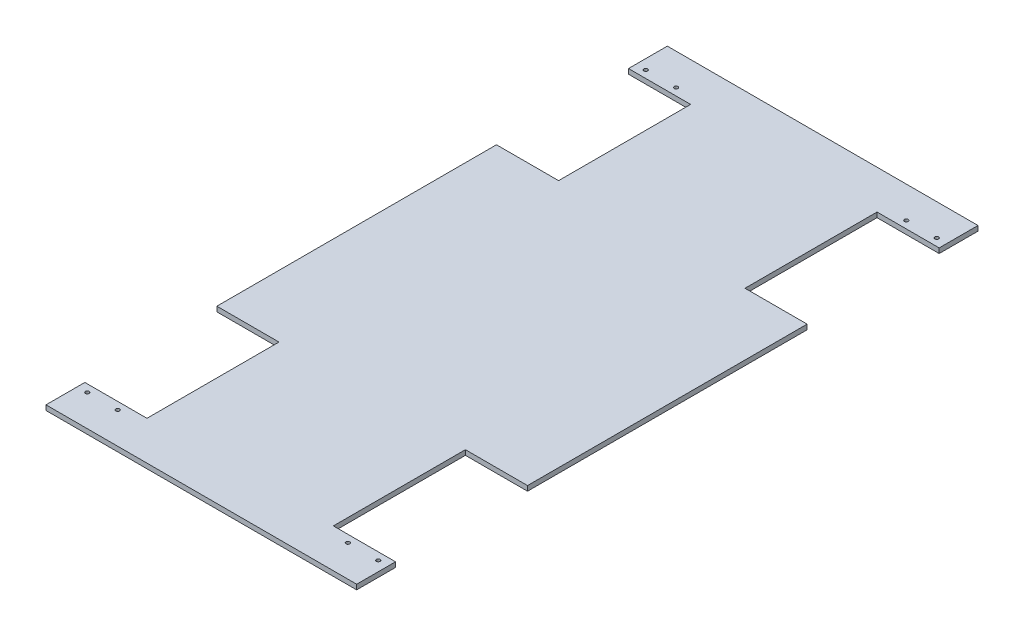
SolidWorks part; units mm, degrees
material "Thornel Mat VMA"
ref_plane "Front Plane" through (0, 0, 0) normal (0, 0, 1) x (1, 0, 0)
ref_plane "Top Plane" through (0, 0, 0) normal (0, 1, 0) x (1, 0, 0)
ref_plane "Right Plane" through (0, 0, 0) normal (1, 0, 0) x (0, 0, -1)
sketch "Sketch1" plane through (0, 0, 0) normal (0, 1, 0) x (1, 0, 0)
  line L0 (-100, 90) -> (-100, -90)
  line L1 (-100, 200) -> (100, 200)
  line L2 (-100, 200) -> (-100, 175)
  line L3 (-100, -200) -> (100, -200)
  line L4 (100, 200) -> (100, 175)
  line L5 (-100, 175) -> (-60, 175)
  line L7 (-100, 90) -> (-60, 90)
  line L8 (-60, 175) -> (-60, 90)
  line L9 (-100, -90) -> (-60, -90)
  line L11 (-100, -175) -> (-60, -175)
  line L12 (-60, -90) -> (-60, -175)
  line L13 (100, -175) -> (60, -175)
  line L15 (100, -90) -> (60, -90)
  line L17 (100, 175) -> (60, 175)
  line L19 (100, 90) -> (60, 90)
  line L20 (60, 175) -> (60, 90)
  line L21 (-100, -175) -> (-100, -200)
  line L22 (100, 90) -> (100, -90)
  line L23 (100, -175) -> (100, -200)
  line L24 (60, -90) -> (60, -175)
  point P4 (0, 200)
  point P6 (100, 0)
  dimension "D1" = 400
  dimension "D2" = 200
  dimension "D3" = 85
  dimension "D4" = 25
  dimension "D5" = 40
extrude "Boss-Extrude1" add sketch "Sketch1" along normal blind 3.175
hole_wizard "3/32 (0.09375) Diameter Hole1" positions "Sketch3" profile "Sketch4" hole size "3/32" standard "ANSI Inch" end condition up to next
sketch "Sketch3" plane through (0, 3.175, 0) normal (0, 1, 0) x (1, 0, 0)
  line L0 (-93.65, 179.7625) -> (-74.09, 179.7625) construction
  line L2 (-83.87, 175) -> (-83.87, 184.525) construction
  line L4 (-100, 200) -> (-100, 175) construction
  point P0 (-93.65, 179.7625)
  point P2 (-74.09, 179.7625)
  point P29 (-83.87, 179.7625)
  point P30 (-83.87, 179.7625)
  dimension "D1" = 19.56
  dimension "D2" = 9.525
  dimension "D3" = 6.35
sketch "Sketch4" plane through (-93.65, 3.175, -179.7625) normal (1, 0, 0) x (0, 0, 1)
  line L0 (0, 0) -> (0, 3.175)
  line L1 (0, 3.175) -> (1.1906, 3.175)
  line L2 (1.1906, 3.175) -> (1.1906, 0)
  line L5 (1.1906, 0) -> (0, 0)
  line L11 (0, -6.35) -> (0, 107.95) construction
  dimension "Thru Hole Dia." = 2.3812
  dimension "Thru Hole Depth" = 3.175
mirror "Mirror5" about plane through (0, 0, 0) normal (1, 0, 0) of "3/32 (0.09375) Diameter Hole1" second plane through (0, 0, 0) second plane normal (0, 0, 1)
sketch "Sketch5" [suppressed] plane through (0, 3.175, 0) normal (0, 1, 0) x (1, 0, 0)
  line L3 (-49.779, 59.6) -> (-93.65, 59.6)
  line L4 (-93.65, 59.6) -> (-93.65, 0)
  line L5 (-93.65, 0) -> (-4.532, 0)
  line L6 (-4.532, 0) -> (-49.779, 59.6)
  line L9 (-53.65, 178.5959) -> (-53.65, 83.9613)
  line L10 (-53.65, 83.9613) -> (-6.35, 130)
  line L11 (-6.35, 130) -> (-53.65, 178.5959)
  line L12 (-53.65, 75.2005) -> (0, 127.4199)
  line L13 (0, 127.4199) -> (0, 4.532)
  line L14 (0, 4.532) -> (-53.65, 75.2005)
  line L15 (-93.65, 193.65) -> (-93.65, 187.7)
  line L16 (-93.65, 187.7) -> (-53.65, 187.7)
  line L17 (-53.65, 187.7) -> (0, 132.5801)
  line L18 (0, 132.5801) -> (0, 193.65)
  line L19 (0, 193.65) -> (-93.65, 193.65)
  line L20 (-60, 175) -> (-60, 85) construction
  line L21 (0, 127.4199) -> (0, 132.5801) construction
  line L22 (100, 200) -> (-100, 200) construction
  line L23 (-100, 85) -> (-100, -85) construction
  line L24 (-100, 200) -> (-100, 175) construction
  line L25 (-100, 175) -> (-60, 175) construction
  line L26 (-60, 85) -> (-100, 85) construction
  line L27 (-4.532, 0) -> (0, 0) construction
  line L28 (0, 0) -> (0, 4.532) construction
  point P9 (0, 130)
  point P19 (-60, 130)
  dimension "D1" = 6.35
  dimension "D2" = 6.35
  dimension "D3" = 6.35
  dimension "D4" = 6.35
  dimension "D5" = 12.7
  dimension "D6" = 25.4
  dimension "D7" = 6.35
  dimension "D8" = 6.35
  dimension "D9" = 6.35
extrude "Cut-Extrude1" [suppressed] cut sketch "Sketch5" against normal through all both and the other way through all
mirror "Mirror6" [suppressed] about plane through (0, 0, 0) normal (1, 0, 0) second plane through (0, 0, 0) second plane normal (0, 0, 1)
